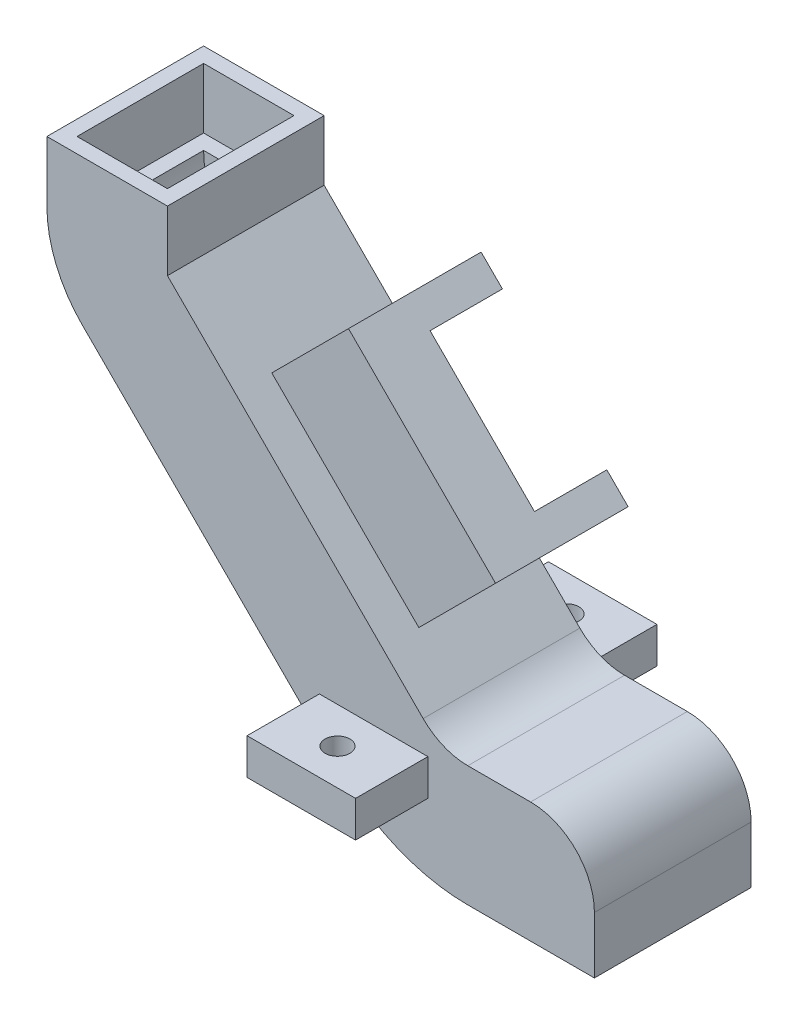
SolidWorks part; units mm, degrees
ref_plane "Front Plane" through (0, 0, 0) normal (0, 0, 1) x (1, 0, 0)
ref_plane "Top Plane" through (0, 0, 0) normal (0, 1, 0) x (1, 0, 0)
ref_plane "Right Plane" through (0, 0, 0) normal (1, 0, 0) x (0, 0, -1)
sketch "Sketch1" plane through (0, 0, 0) normal (0, 0, 1) x (1, 0, 0)
  line L0 (0, 0) -> (-44.5176, 44.5176) construction
  line L1 (-40.982, 48.0531) -> (-48.0531, 40.982) construction
  line L2 (-40.982, 48.0531) -> (1.4444, 5.6267)
  line L3 (12.3925, 6.0918) -> (22.8046, 6.0918)
  line L4 (-48.0531, 40.982) -> (-5.6267, -1.4444)
  line L5 (0, 0) -> (-7.0711, 0) construction
  line L6 (-40.982, 48.0531) -> (-37.4465, 51.5886) construction
  line L7 (-5.6267, -1.4444) -> (-9.1622, -4.9799) construction
  line L8 (12.3925, 1.0918) -> (22.8046, 1.0918)
  line L9 (-52.4465, 51.5886) -> (-57.4465, 51.5886)
  line L10 (-48.0531, 40.982) -> (-51.5886, 37.4465) construction
  line L11 (-51.5886, 37.4465) -> (-9.1622, -4.9799)
  line L12 (28.3925, -4.4961) -> (28.3925, -13.9082)
  line L13 (-42.4465, 51.5886) -> (-37.4465, 51.5886)
  line L14 (-37.4465, 51.5886) -> (4.9799, 9.1622)
  line L15 (4.9799, 9.1622) -> (1.4444, 5.6267) construction
  line L16 (12.3925, -8.9082) -> (12.3925, -13.9082)
  line L17 (12.3925, 16.5748) -> (4.9799, 9.1622) construction
  line L18 (-5.6267, -1.4444) -> (12.3925, 16.5748) construction
  line L19 (28.3925, -13.9082) -> (33.3925, -13.9082)
  line L20 (33.3925, -13.9082) -> (33.3925, -4.4961)
  arc A0 (-40.982, 48.0531) -> (-42.4465, 51.5886) centre (-37.4465, 51.5886) cw
  arc A1 (-5.6267, -1.4444) -> (12.3925, -8.9082) centre (12.3925, 16.5748) ccw
  arc A2 (-48.0531, 40.982) -> (-52.4465, 51.5886) centre (-37.4465, 51.5886) cw
  arc A3 (-9.1622, -4.9799) -> (12.3925, -13.9082) centre (12.3925, 16.5748) ccw
  arc A4 (-57.4465, 51.5886) -> (-51.5886, 37.4465) centre (-37.4465, 51.5886) ccw
  arc A5 (4.9799, 9.1622) -> (12.3925, 6.0918) centre (12.3925, 16.5748) ccw
  arc A6 (1.4444, 5.6267) -> (12.3925, 1.0918) centre (12.3925, 16.5748) ccw
  arc A7 (22.8046, 6.0918) -> (33.3925, -4.4961) centre (22.8046, -4.4961) cw
  arc A8 (22.8046, 1.0918) -> (28.3925, -4.4961) centre (22.8046, -4.4961) cw
  point P4 (-44.5176, 44.5176)
  dimension "D7" = 16
  dimension "D1" = 45
  dimension "D2" = 10
  dimension "D3" = 5
  dimension "D4" = 5
  dimension "D5" = 5
  dimension "D6" = 60
extrude "Boss-Extrude1" add sketch "Sketch1" along normal blind 16
sketch "Sketch5" plane through (0, 0, 16) normal (0, 0, 1) x (1, 0, 0)
  line L0 (-57.4465, 51.5886) -> (-37.4465, 51.5886)
  line L1 (-37.4465, 51.5886) -> (4.9799, 9.1622)
  line L2 (12.3925, 6.0918) -> (22.8046, 6.0918)
  line L3 (33.3925, -13.9082) -> (33.3925, -4.4961) construction
  line L4 (33.3925, -4.4961) -> (33.3925, -13.9082)
  line L5 (33.3925, -13.9082) -> (12.3925, -13.9082)
  line L6 (-9.1622, -4.9799) -> (-51.5886, 37.4465)
  arc A0 (4.9799, 9.1622) -> (12.3925, 6.0918) centre (12.3925, 16.5748) ccw
  arc A1 (22.8046, 6.0918) -> (33.3925, -4.4961) centre (22.8046, -4.4961) cw
  arc A2 (33.3925, -4.4961) -> (22.8046, 6.0918) centre (22.8046, -4.4961) ccw construction
  arc A3 (12.3925, -13.9082) -> (-9.1622, -4.9799) centre (12.3925, 16.5748) cw
  arc A4 (-51.5886, 37.4465) -> (-57.4465, 51.5886) centre (-37.4465, 51.5886) cw
extrude "Boss-Extrude4" add sketch "Sketch5" along normal blind 5
sketch "Sketch6" plane through (0, 0, 0) normal (0, 0, -1) x (-1, 0, 0)
  line L0 (-4.9799, 9.1622) -> (37.4465, 51.5886)
  line L1 (37.4465, 51.5886) -> (57.4465, 51.5886)
  line L2 (51.5886, 37.4465) -> (9.1622, -4.9799)
  line L3 (-12.3925, -13.9082) -> (-33.3925, -13.9082)
  line L4 (-33.3925, -13.9082) -> (-33.3925, -4.4961)
  line L5 (-22.8046, 6.0918) -> (-12.3925, 6.0918)
  line L6 (-22.8046, 6.0918) -> (-12.3925, 6.0918) construction
  line L7 (28.6077, 35.6787) -> (10.93, 18.001)
  line L8 (40.982, 48.0531) -> (-1.4444, 5.6267) construction
  line L9 (10.93, 18.001) -> (18.001, 10.93)
  line L10 (5.6267, -1.4444) -> (48.0531, 40.982) construction
  line L11 (18.001, 10.93) -> (35.6787, 28.6077)
  line L12 (35.6787, 28.6077) -> (28.6077, 35.6787)
  line L13 (40.982, 48.0531) -> (-1.4444, 5.6267) construction
  arc A0 (51.5886, 37.4465) -> (57.4465, 51.5886) centre (37.4465, 51.5886) ccw construction
  arc A1 (57.4465, 51.5886) -> (51.5886, 37.4465) centre (37.4465, 51.5886) cw
  arc A2 (9.1622, -4.9799) -> (-12.3925, -13.9082) centre (-12.3925, 16.5748) cw
  arc A3 (-33.3925, -4.4961) -> (-22.8046, 6.0918) centre (-22.8046, -4.4961) cw
  arc A4 (-12.3925, 6.0918) -> (-4.9799, 9.1622) centre (-12.3925, 16.5748) ccw construction
  arc A5 (-12.3925, 6.0918) -> (-4.9799, 9.1622) centre (-12.3925, 16.5748) ccw
  point P34 (19.7688, 26.8399)
  dimension "D1" = 25
extrude "Boss-Extrude5" add sketch "Sketch6" along normal blind 5
sketch "Sketch7" plane through (0, 51.5886, 0) normal (0, 1, 0) x (1, 0, 0)
  line L1 (-57.4465, 5) -> (-37.4465, 5)
  line L2 (-57.4465, 5) -> (-57.4465, -21)
  line L3 (-57.4465, -21) -> (-37.4465, -21)
  line L4 (-37.4465, 5) -> (-37.4465, -21)
  line L5 (-54.9465, 2.5) -> (-39.9465, 2.5)
  line L6 (-54.9465, 2.5) -> (-54.9465, -18.5)
  line L7 (-54.9465, -18.5) -> (-39.9465, -18.5)
  line L8 (-39.9465, 2.5) -> (-39.9465, -18.5)
  dimension "D1" = 2.5
  dimension "D2" = 2.5
  dimension "D3" = 2.5
  dimension "D4" = 2.5
extrude "Boss-Extrude6" add sketch "Sketch7" along normal blind 10
sketch "Sketch9" plane through (7.0711, 7.0711, 0) normal (0.7071, 0.7071, 0) x (0, 0, -1)
  line L0 (-15, 32.9573) -> (-5, 32.9573) construction
  line L1 (-15, 46.9573) -> (-5, 46.9573)
  line L2 (-15, 46.9573) -> (-15, 12.4573)
  line L3 (-15, 12.4573) -> (-5, 12.4573)
  line L4 (-5, 46.9573) -> (-5, 12.4573)
  line L5 (5, 62.9573) -> (5, 2.9573) construction
  point P8 (5, 32.9573)
  dimension "D1" = 34.5
  dimension "D2" = 20.5
  dimension "D3" = 10
  dimension "D4" = 10
extrude "Boss-Extrude7" add sketch "Sketch9" along normal blind 18
sketch "Sketch10" plane through (0, 0, 5) normal (0, 0, -1) x (-1, 0, 0)
  line L0 (20.8295, 45.5782) -> (17.2939, 42.0427)
  line L1 (13.4049, 53.0028) -> (26.1328, 40.2749) construction
  line L2 (17.2939, 42.0427) -> (9.8693, 49.4673)
  line L3 (-10.9903, 28.6077) -> (13.4049, 53.0028) construction
  line L4 (9.8693, 49.4673) -> (13.4049, 53.0028)
  line L5 (13.4049, 53.0028) -> (20.8295, 45.5782)
  line L6 (-10.9903, 28.6077) -> (-7.4548, 32.1432)
  line L7 (-7.4548, 32.1432) -> (-0.0302, 24.7186)
  line L8 (-0.0302, 24.7186) -> (-3.5657, 21.183)
  line L9 (-10.9903, 28.6077) -> (1.7376, 15.8797) construction
  line L10 (-3.5657, 21.183) -> (-10.9903, 28.6077)
  line L11 (-0.0302, 24.7186) -> (17.2939, 42.0427) construction
  line L13 (10.5764, 35.3252) -> (3.1518, 42.7498) construction
  line L14 (1.7376, 15.8797) -> (26.1328, 40.2749) construction
  point P20 (-3.7425, 28.4309)
  dimension "D1" = 5
  dimension "D2" = 5
  dimension "D3" = 10.5
  dimension "D5" = 15
  dimension "D6" = 7.5
extrude "Boss-Extrude8" add sketch "Sketch10" along normal blind 12
sketch "Sketch11" plane through (0, 0, -5) normal (0, 0, -1) x (-1, 0, 0)
  line L0 (19.7688, 26.8399) -> (14.3563, 32.2524) construction
  line L1 (40.982, 48.0531) -> (-1.4444, 5.6267) construction
  line L2 (24.365, 31.4361) -> (20.8295, 34.9716)
  line L3 (1.7376, 15.8797) -> (26.1328, 40.2749) construction
  line L5 (20.8295, 34.9716) -> (16.2333, 30.3754)
  line L6 (24.365, 31.4361) -> (19.7688, 26.8399)
  line L7 (9.8693, 49.4673) -> (17.2939, 42.0427) construction
  line L8 (16.2333, 30.3754) -> (9.5158, 23.6579)
  line L9 (9.5158, 23.6579) -> (13.0513, 20.1224)
  line L10 (13.0513, 20.1224) -> (19.7688, 26.8399)
  point P10 (11.2835, 21.8901)
  dimension "D1" = 6.5
  dimension "D2" = 9.5
extrude "Cut-Extrude3" cut sketch "Sketch11" against normal up to surface (10 mm away) up to face at (-8.1016, 33.911, 5)
sketch "Sketch12" plane through (0, 0, 21) normal (0, 0, 1) x (1, 0, 0)
  line L0 (16.0503, -1.9082) -> (-12.234, -1.9082) construction
  line L4 (-26.1328, 40.2749) -> (-1.7376, 15.8797) construction
  line L5 (-51.5886, 37.4465) -> (-9.1622, -4.9799) construction
  line L6 (-12.234, -1.9082) -> (5.766, -1.9082)
  line L7 (5.766, -1.9082) -> (5.766, 4.0918)
  line L8 (5.766, 4.0918) -> (-12.234, 4.0918)
  line L9 (-12.234, 4.0918) -> (-12.234, -1.9082)
  line L10 (12.3925, -13.9082) -> (33.3925, -13.9082) construction
  dimension "D1" = 18
  dimension "D2" = 6
  dimension "D3" = 12
extrude "Boss-Extrude9" add sketch "Sketch12" along normal blind 12
sketch "Sketch13" plane through (0, 4.0918, 0) normal (0, 1, 0) x (1, 0, 0)
  line L0 (5.766, -33) -> (-12.234, -33) construction
  line L1 (5.766, -33) -> (5.766, -21) construction
  circle A0 centre (-3.234, -27) radius 2.0625
  point P5 (-3.234, -33)
  point P9 (5.766, -27)
  dimension "D1" = 4.125
extrude "Cut-Extrude4" cut sketch "Sketch13" against normal blind 18
sketch "Sketch14" plane through (0, 0, 0) normal (0, 1, 0) x (1, 0, 0)
  line L0 (28.3925, -8) -> (12.3925, -8) construction
  line L1 (12.3925, -21) -> (33.3925, -21) construction
  line L2 (28.3925, -16) -> (28.3925, 0) construction
  line L3 (-3.234, -27) -> (20.3925, -27) construction
  line L4 (12.3925, -16) -> (12.3925, 0) construction
  line L6 (20.3925, -8) -> (20.3925, -27) construction
  dimension "D1" = 23.6265
  dimension "D2" = 19
  dimension "D3" = 13
ref_plane "Plane1" through (0, 0, 8) normal (0, 0, 1) x (1, 0, 0)
mirror "Mirror1" about plane through (0, 0, 8) normal (0, 0, 1) of "Cut-Extrude4", "Boss-Extrude9"
sketch "Sketch15" plane through (0, 0, 0) normal (0, 0, 1) x (1, 0, 0)
  line L0 (5.766, -1.9082) -> (5.766, -13.9082) construction
  line L1 (5.766, -13.9082) -> (33.3925, -13.9082) construction
  point P3 (0, 0)
  dimension "D1" = 12
